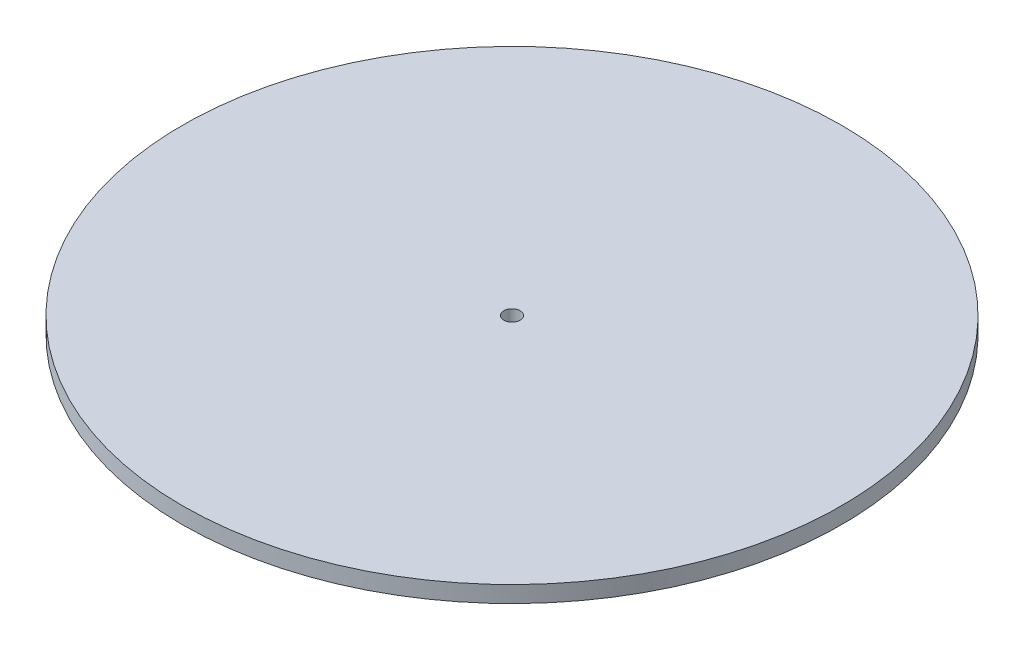
SolidWorks part; units mm, degrees
ref_plane "Front Plane" through (0, 0, 0) normal (0, 0, 1) x (1, 0, 0)
ref_plane "Top Plane" through (0, 0, 0) normal (0, 1, 0) x (1, 0, 0)
ref_plane "Right Plane" through (0, 0, 0) normal (1, 0, 0) x (0, 0, -1)
sketch "Sketch1" plane through (0, 0, 0) normal (0, 1, 0) x (1, 0, 0)
  circle A0 centre (0, 0) radius 127
  circle A1 centre (0, 0) radius 3.175
  dimension "D1" = 6.35
  dimension "D2" = 254
extrude "Boss-Extrude1" add sketch "Sketch1" along normal blind 6.35
